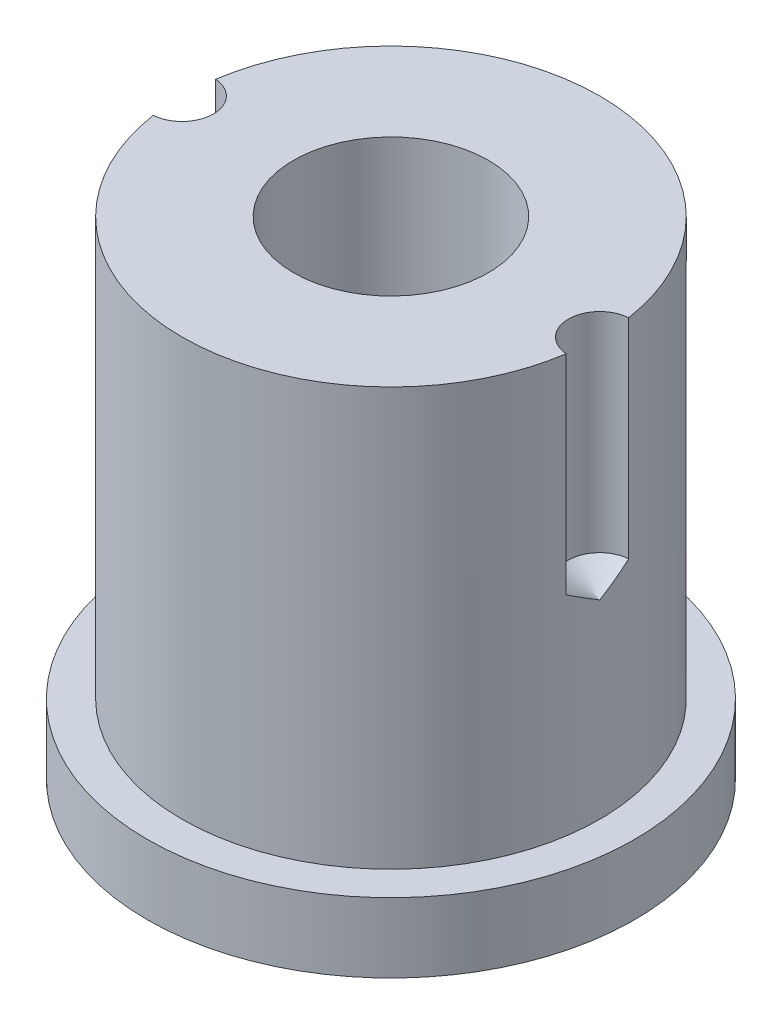
SolidWorks part; units mm, degrees
material "Commercial Bronze, UNS C22000 (90-10 Bronze)"
ref_plane "Front Plane" through (0, 0, 0) normal (0, 0, 1) x (1, 0, 0)
ref_plane "Top Plane" through (0, 0, 0) normal (0, 1, 0) x (1, 0, 0)
ref_plane "Right Plane" through (0, 0, 0) normal (1, 0, 0) x (0, 0, -1)
sketch "Sketch1" plane through (0, 0, 0) normal (0, 1, 0) x (1, 0, 0)
  circle A0 centre (0, 0) radius 35
  dimension "D1" = 70
extrude "Boss-Extrude1" add sketch "Sketch1" along normal blind 10
sketch "Sketch2" plane through (0, 10, 0) normal (0, 1, 0) x (1, 0, 0)
  circle A0 centre (0, 0) radius 30
  dimension "D1" = 60
extrude "Boss-Extrude2" add sketch "Sketch2" along normal blind 60
sketch "Sketch3" plane through (0, 70, 0) normal (0, 1, 0) x (1, 0, 0)
  circle A0 centre (0, 0) radius 14
  dimension "D1" = 28
extrude "Cut-Extrude1" cut sketch "Sketch3" against normal through all
hole_wizard "Ø8.0mm Dowel Hole1" positions "Sketch4" profile "Sketch5" hole size "Ø8.0" standard "ISO"
sketch "Sketch4" plane through (0, 70, 0) normal (0, 1, 0) x (1, 0, 0)
  circle A0 centre (0, 0) radius 30 construction
  circle A1 centre (0, 0) radius 30 construction
  point P0 (-30, 0)
  point P4 (30, 0)
sketch "Sketch5" plane through (-30, 70, 0) normal (1, 0, 0) x (0, 0, 1)
  line L0 (0, 0) -> (0, 32.7039)
  line L1 (0, 32.7039) -> (4.5, 30)
  line L2 (4.5, 30) -> (4.5, 0)
  line L5 (4.5, 0) -> (0, 0)
  line L10 (0, 32.7039) -> (-4.5, 30) construction
  line L11 (0, -6.35) -> (0, 107.95) construction
  dimension "Hole Dia." = 9
  dimension "Hole Depth" = 30
  dimension "Drill Angle" = 118
